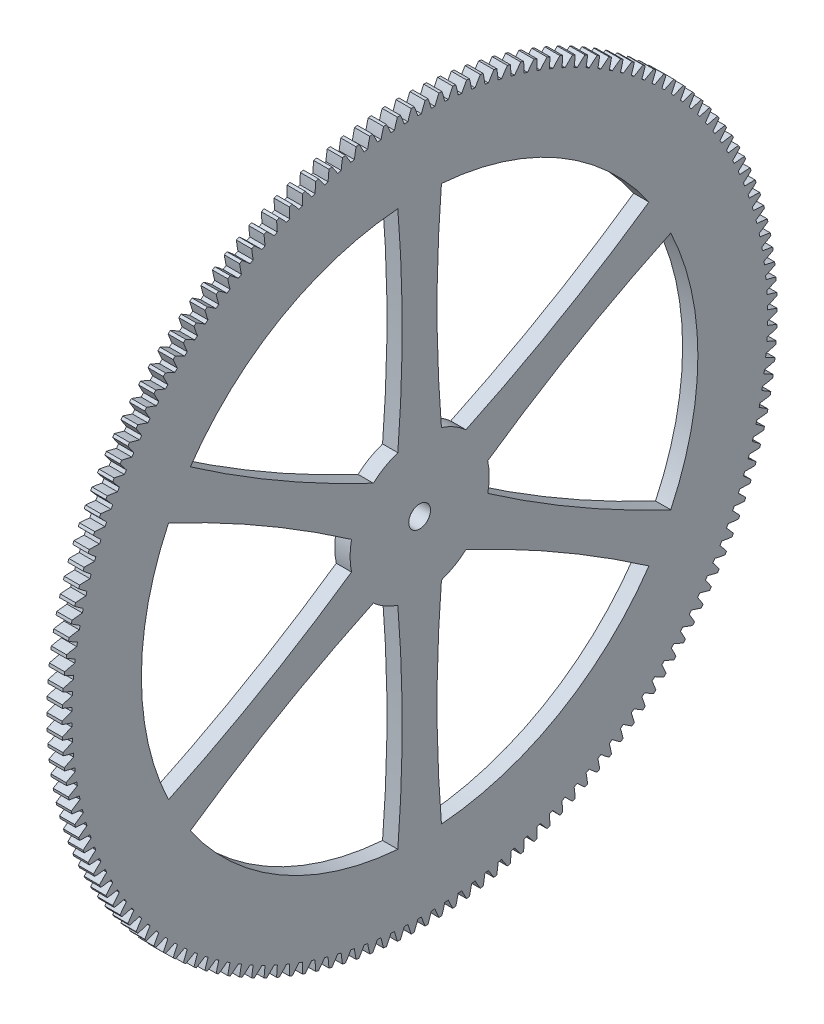
SolidWorks part; units mm, degrees
material "Cedar"
ref_plane "Plane1" through (0, 0, 0) normal (0, 0, 1) x (1, 0, 0)
ref_plane "Plane2" through (0, 0, 0) normal (0, 1, 0) x (1, 0, 0)
ref_plane "Plane3" through (0, 0, 0) normal (1, 0, 0) x (0, 0, -1)
sketch "HoldingSke" plane through (0, 0, 0) normal (0, 1, 0) x (1, 0, 0)
  line L0 (0, 0) -> (-483.1367, -156.9806)
  line L1 (-15, 0) -> (100, 0) construction
  line L2 (0, 0) -> (-2.1039, 2.3779)
  line L3 (0, 0) -> (-11.863, 4.5341)
  line L4 (0, 0) -> (-8.2133, 2.6687)
  line L5 (0, 0) -> (-47.5972, -17.7524)
  line L6 (0, 0) -> (-3.6847, -2.4861)
  line L7 (-2.1039, 2.3779) -> (8.8308, 51.9871)
  line L8 (-76.2, 54.61) -> (-69.596, 54.61)
  line L9 (-71.009, 38.7566) -> (-53.1078, 45.2721)
  line L10 (-76.2, 71.12) -> (104.1128, 71.12)
  line L11 (0, 0) -> (-4.445, 0)
  line L12 (-76.2, 101.6) -> (-76.1492, 101.6)
  line L13 (24.9733, 27.94) -> (52.9518, 28.4284)
  line L14 (24.9733, 27.94) -> (25.0241, 27.9398)
  line L15 (24.9733, 27.94) -> (100.4021, 29.52)
  circle A0 centre (0, 0) radius 3.175
  circle A1 centre (0, 0) radius 38.1
  circle A2 centre (0, 0) radius 38.1
  circle A3 centre (0, 0) radius 3.175
  dimension "MHD" = 76.2
  dimension "Hub_dia" = 76.2
  dimension "Bore" = 6.35
  dimension "MBD" = 6.35
  dimension "Num_teeth" = 162
  dimension "Pitch_radius" = 180.3128
  dimension "Pitch" = 508
  dimension "Width" = 4.445
  dimension "Overall_len" = 50.8
  dimension "Show_teeth" = 162
  dimension "Thickness" = 4.445
  dimension "OAL" = 50.8001
  dimension "T_dim" = 6.604
  dimension "Ap" = 20
  dimension "H" = 19.05
  dimension "Backlash" = 0.0508
  dimension "Addendum_fac" = 1
  dimension "Dedendum_fac" = 1.2
  dimension "Clearance_fac" = 0.2
  dimension "Dedendum_add" = 0.0508
sketch "BasProSke" plane through (0, 0, 0) normal (0, 1, 0) x (1, 0, 0)
  line L0 (-10, 0) -> (60, 0) construction
  line L1 (0, 0) -> (0, 104.14)
  line L2 (0, 0) -> (4.445, 0)
  line L3 (4.445, 0) -> (4.445, 104.14)
  line L4 (4.445, 104.14) -> (0, 104.14)
  dimension "Diameter" = 208.28
  dimension "Thickness" = 4.445
revolve "Base-Revolve" add sketch "BasProSke" angle 360 about L0
sketch "TooCutSke" plane through (0, 0, 0) normal (1, 0, 0) x (0, 0, -1)
  line L1 (0, 0) -> (0, 107) construction
  line L2 (0, 0) -> (-1.0863, 102.8643) construction
  line L3 (0, 0) -> (-3.9894, 205.6933) construction
  line L4 (-1.0863, 102.8643) -> (-1.9947, 102.8466) construction
  arc A0 (0.524, 101.2938) -> (-0.524, 101.2938) centre (0, 0) ccw
  arc A1 (1.6026, 104.1531) -> (-1.6026, 104.1531) centre (0, 0) ccw
  circle A2 centre (0, 0) radius 102.87 construction
  circle A3 centre (0, 0) radius 96.6662 construction
  arc A4 (-0.524, 101.2938) -> (-1.6026, 104.1531) centre (-39.5368, 88.211) ccw
  arc A5 (1.6026, 104.1531) -> (0.524, 101.2938) centre (39.5368, 88.211) ccw
  dimension "Root_dia" = 202.5904
  dimension "Overcut_dia" = 208.3308
  dimension "Pitch_dia" = 205.74
  dimension "Base_dia" = 193.3324
  dimension "Flank_rad" = 41.148
  dimension "Half_ang" = 1.111
  dimension "Half_CT" = 0.9085
extrude "ToothCut" cut sketch "TooCutSke" along normal through all
fillet "Breaks" [suppressed] radius 0.0254
fillet "RootFillets" [suppressed] radius 0.3048
pattern_circular "TeethCuts" count 162 every 2.222 about axis through (-10, 0, 0) along (1, 0, 0) of "ToothCut", "RootFillets", "Breaks"
sketch "HubNeaOneSke" plane through (0, 0, 0) normal (-1, 0, 0) x (0, 0, 1)
  circle A0 centre (0, 0) radius 38.1
  dimension "Diameter" = 76.2
extrude "HubNearOne" [suppressed] add sketch "HubNeaOneSke" along normal blind 46.3551
sketch "HubNeaBotSke" plane through (0, 0, 0) normal (-1, 0, 0) x (0, 0, 1)
  circle A0 centre (0, 0) radius 38.1
  dimension "Diameter" = 76.2
extrude "HubNearBoth" [suppressed] add sketch "HubNeaBotSke" along normal blind 23.1775
ref_plane "FarPln" through (4.445, 0, 0) normal (1, 0, 0) x (0, 0, -1)
sketch "HubFarSke" plane through (4.445, 0, 0) normal (1, 0, 0) x (0, 0, -1)
  circle A0 centre (0, 0) radius 38.1
  dimension "Diameter" = 76.2
extrude "HubFar" [suppressed] add sketch "HubFarSke" along normal blind 23.1775
sketch "BorSke" plane through (0, 0, 0) normal (1, 0, 0) x (0, 0, -1)
  circle A0 centre (0, 0) radius 3.175
  dimension "Diameter" = 6.35
extrude "Bore" cut sketch "BorSke" along normal mid plane 101.6001
sketch "KeySke" plane through (0, 0, 0) normal (1, 0, 0) x (0, 0, -1)
  line L0 (-0.127, 0) -> (-0.127, 3.429)
  line L1 (-0.127, 3.429) -> (0.127, 3.429)
  line L2 (0.127, 3.429) -> (0.127, 0)
  line L3 (0, 0) -> (0, 34) construction
  line L4 (-0.127, 0) -> (0.127, 0)
  dimension "Offset" = 3.429
  dimension "Width" = 0.254
extrude "Keyway" [suppressed] cut sketch "KeySke" along normal mid plane 101.6001
pattern_circular "Keyway2" [suppressed] count 2 every 90 about axis through (-10, 0, 0) along (1, 0, 0)
sketch "Sketch1" plane through (4.445, 0, 0) normal (1, 0, 0) x (0, 0, -1)
  circle A0 centre (0, 0) radius 102.87
  dimension "D1" = 205.74
sketch "Sketch2" plane through (4.445, 0, 0) normal (1, 0, 0) x (0, 0, -1)
  line L0 (-6.35, 80.787) -> (-6.35, 19.2381)
  line L1 (-6.35, 80.787) -> (6.35, 80.787)
  line L2 (-6.35, 19.2381) -> (6.35, 19.2381)
  line L3 (6.35, 80.787) -> (6.35, 19.2381)
  circle A0 centre (0, 0) radius 20.259
  circle A1 centre (0, 0) radius 81.0362
  arc A2 (-6.35, 19.2381) -> (-6.35, 80.787) centre (-378.5752, 50.0126) ccw
  arc A3 (6.35, 19.2381) -> (6.35, 80.787) centre (378.5752, 50.0126) cw
  arc A4 (13.4857, 15.1183) -> (66.7886, 45.8928) centre (-145.9754, 352.862) ccw
  arc A5 (19.8357, 4.1198) -> (73.1386, 34.8942) centre (232.5997, -302.8495) cw
  arc A6 (19.8357, -4.1198) -> (73.1386, -34.8942) centre (232.5997, 302.8495) ccw
  arc A7 (13.4857, -15.1183) -> (66.7886, -45.8928) centre (-145.9754, -352.862) cw
  arc A8 (6.35, -19.2381) -> (6.35, -80.787) centre (378.5752, -50.0126) ccw
  arc A9 (-6.35, -19.2381) -> (-6.35, -80.787) centre (-378.5752, -50.0126) cw
  arc A10 (-13.4857, -15.1183) -> (-66.7886, -45.8928) centre (145.9754, -352.862) ccw
  arc A11 (-19.8357, -4.1198) -> (-73.1386, -34.8942) centre (-232.5997, 302.8495) cw
  arc A12 (-19.8357, 4.1198) -> (-73.1386, 34.8942) centre (-232.5997, -302.8495) ccw
  arc A13 (-13.4857, 15.1183) -> (-66.7886, 45.8928) centre (145.9754, 352.862) cw
  point P8 (-5.08, 50.0126)
  point P9 (5.08, 50.0126)
  point P45 (0, 0)
  dimension "D1" = 40.5181
  dimension "D2" = 162.0723
  dimension "D4" = 10.16
  dimension "D3" = 12.7
  dimension "D5" = 6
extrude "Cut-Extrude1" cut sketch "Sketch2" against normal through all contours A13 A0 L0 A1 | A0 A4 A1 L3 | A0 A6 A1 A5 | A0 A8 A1 A7 | A0 A10 A1 A9 | A0 A12 A1 A11 | L0 A2 | A3 L3
equation "' \"Pitch@HoldingSke\" = 4"
equation "' \"Num_teeth@HoldingSke\" = 12"
equation "' \"Ap@HoldingSke\" =  20"
equation "' \"Width@HoldingSke\" = 0.5"
equation "' \"Hub_dia@HoldingSke\"= 1"
equation "' \"Overall_len@HoldingSke\" = 1.0"
equation "' \"Bore@HoldingSke\" = 0.75"
equation "' \"T_dim@HoldingSke\" = 0.85"
equation "' \"Width@KeySke\" = 0.25"
equation "' \"Show_teeth@HoldingSke\" = 13"
equation "' \"Backlash@HoldingSke\" = 0.009"
equation "' \"Addendum_fac@HoldingSke\" = 1.0"
equation "' \"Dedendum_fac@HoldingSke\" = 1.25"
equation "' \"Dedendum_add@HoldingSke\" = 0.00005"
equation "' \"Clearance_fac@HoldingSke\" = 0.25"
equation "' \"Pitch@HoldingSke\" = 0.5"
equation "' \"Num_teeth@HoldingSke\" = 23"
equation "' \"Show_teeth@HoldingSke\" = 23"
equation "' \"Backlash@HoldingSke\" = 0.0375"
equation "\"Overcut_dia@TooCutSke\" = (\"Num_teeth@HoldingSke\" + 2 * \"Addendum_fac@HoldingSke\") / \"Pitch@HoldingSke\" + 0.002"
equation "\"Pitch_dia@TooCutSke\" = \"Num_teeth@HoldingSke\" / \"Pitch@HoldingSke\""
equation "\"Base_dia@TooCutSke\" = \"Num_teeth@HoldingSke\" / \"Pitch@HoldingSke\" * cos((\"Ap@HoldingSke\"  * 3.14159265 / 180))"
equation "\"Root_dia@TooCutSke\" = (\"Num_teeth@HoldingSke\" + 2) / \"Pitch@HoldingSke\" - 2 * (\"Addendum_fac@HoldingSke\" + \"Dedendum_fac@HoldingSke\") / \"Pitch@HoldingSke\" - \"Dedendum_add@HoldingSke\" * 2"
equation "\"Half_ang@TooCutSke\" = 180 / \"Num_teeth@HoldingSke\""
equation "\"Half_CT@TooCutSke\" = \"Num_teeth@HoldingSke\" / \"Pitch@HoldingSke\" * sin((3.14159265 / 2 / \"Num_teeth@HoldingSke\")) / 2 - 7 * \"Backlash@HoldingSke\" / 4"
equation "\"Flank_rad@TooCutSke\" = \"Num_teeth@HoldingSke\" / \"Pitch@HoldingSke\" / 5"
equation "\"Radius@RootFillets\" = \"Clearance_fac@HoldingSke\" / \"Pitch@HoldingSke\" + \"Dedendum_add@HoldingSke\""
equation "\"Break_rad@Breaks\" = 0.02 / \"Pitch@HoldingSke\""
equation "\"Thickness@HoldingSke\" = \"Width@HoldingSke\""
equation "\"OAL@HoldingSke\" = \"Thickness@HoldingSke\""
equation "\"MHD@HoldingSke\" = (\"Num_teeth@HoldingSke\" + 2) / \"Pitch@HoldingSke\" - 2 * (\"Addendum_fac@HoldingSke\" + \"Dedendum_fac@HoldingSke\")  / \"Pitch@HoldingSke\" - \"Dedendum_add@HoldingSke\" * 2"
equation "\"MBD@HoldingSke\" = (\"Num_teeth@HoldingSke\" + 2) / \"Pitch@HoldingSke\" - 2 * (\"Addendum_fac@HoldingSke\" + \"Dedendum_fac@HoldingSke\")  / \"Pitch@HoldingSke\" - \"Dedendum_add@HoldingSke\" * 2 - 0.002"
equation "\"MHD@HoldingSke\" = ((sgn( \"MHD@HoldingSke\" - \"Hub_dia@HoldingSke\" )-1)*( \"MHD@HoldingSke\" - \"Hub_dia@HoldingSke\" ))/-2+ \"Hub_dia@HoldingSke\""
equation "\"MBD@HoldingSke\" = ((sgn( \"MBD@HoldingSke\" - \"Bore@HoldingSke\" )-1)*( \"MBD@HoldingSke\" - \"Bore@HoldingSke\" ))/-2+ \"Bore@HoldingSke\""
equation "\"OAL@HoldingSke\" = ((sgn( \"OAL@HoldingSke\" - \"Overall_len@HoldingSke\" )+1)*( \"OAL@HoldingSke\" - \"Overall_len@HoldingSke\" ))/2 + \"Overall_len@HoldingSke\" + 0.000002"
equation "\"Num_teeth@TeethCuts\" = int( \"Show_teeth@HoldingSke\" ) + 1"
equation "\"Num_teeth@TeethCuts\" = ((sgn( \"Num_teeth@TeethCuts\" - \"Num_teeth@HoldingSke\" )-1)*( \"Num_teeth@TeethCuts\" - \"Num_teeth@HoldingSke\" ))/-2+ \"Num_teeth@HoldingSke\""
equation "\"Num_teeth@TeethCuts\" = ((sgn( \"Num_teeth@TeethCuts\" - 2.0)+1)*( \"Num_teeth@TeethCuts\" - 2.0))/2 +2.0"
equation "\"Angle@TeethCuts\" = 360.0 / \"Num_teeth@HoldingSke\""
equation "\"Diameter@BasProSke\" = (\"Num_teeth@HoldingSke\" + 2 * \"Addendum_fac@HoldingSke\") / \"Pitch@HoldingSke\""
equation "\"Thickness@BasProSke\"  = \"Thickness@HoldingSke\""
equation "' \"Fillet_rad@BasProSke\" =  \"Thickness@HoldingSke\" * 0.05"
equation "\"MHD@HoldingSke\" = ((sgn( \"MHD@HoldingSke\" - \"Root_dia@TooCutSke\" )-1)*( \"MHD@HoldingSke\" - \"Root_dia@TooCutSke\" ))/-2+ \"Root_dia@TooCutSke\""
equation "\"Diameter@HubNeaOneSke\" = \"MHD@HoldingSke\""
equation "\"Length@HubNearOne\" = \"OAL@HoldingSke\" - \"Thickness@BasProSke\""
equation "\"Diameter@HubNeaBotSke\" = \"MHD@HoldingSke\""
equation "\"Length@HubNearBoth\" = ( \"OAL@HoldingSke\" - \"Thickness@BasProSke\" ) / 2.0"
equation "\"Thickness@FarPln\" = \"Thickness@BasProSke\""
equation "\"Diameter@HubFarSke\" = \"MHD@HoldingSke\""
equation "\"Length@HubFar\" = ( \"OAL@HoldingSke\" - \"Thickness@BasProSke\" ) / 2.0"
equation "\"Diameter@BorSke\" = \"MBD@HoldingSke\""
equation "\"D1@Bore\" = \"OAL@HoldingSke\" * 2.0"
equation "\"D1@Keyway\" = \"OAL@HoldingSke\" * 2.0"
equation "\"Offset@KeySke\" = \"T_dim@HoldingSke\" - \"MBD@HoldingSke\" / 2.0"
